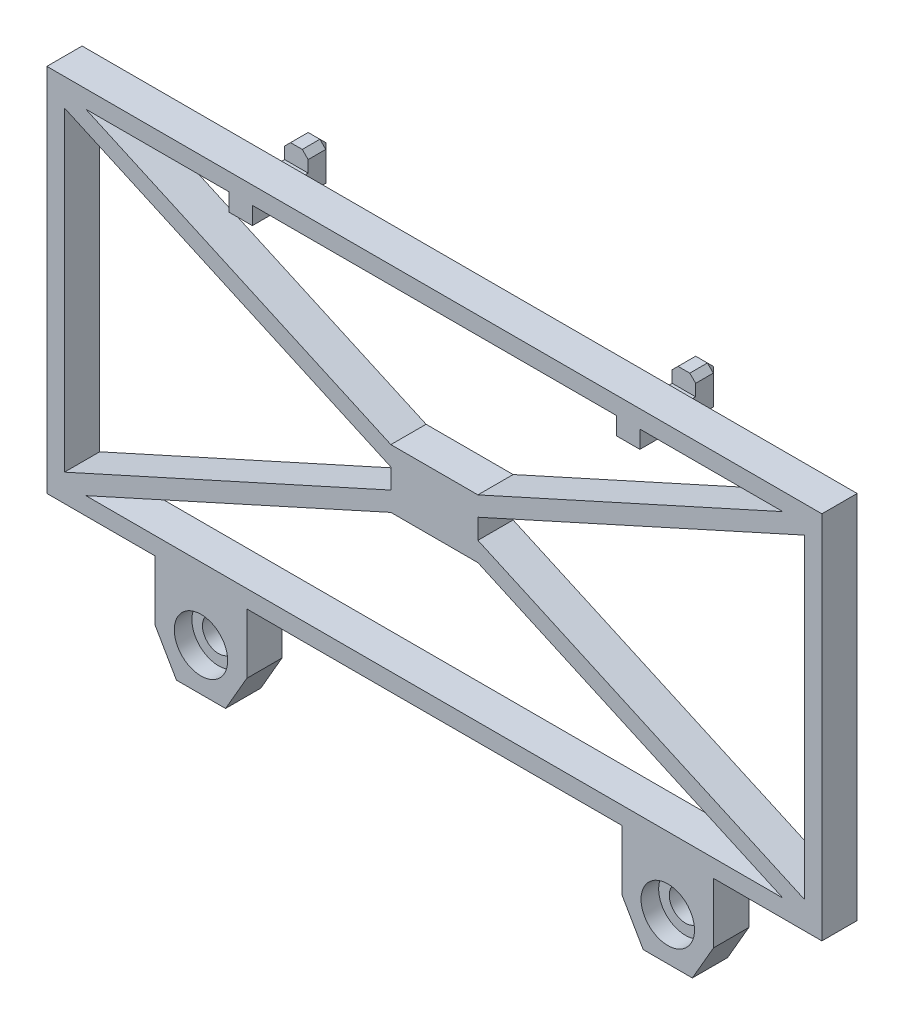
SolidWorks part; units mm, degrees
ref_plane "Front Plane" through (0, 0, 0) normal (0, 0, 1) x (1, 0, 0)
ref_plane "Top Plane" through (0, 0, 0) normal (0, 1, 0) x (1, 0, 0)
ref_plane "Right Plane" through (0, 0, 0) normal (1, 0, 0) x (0, 0, -1)
sketch "Sketch1" plane through (0, 0, 0) normal (0, 0, 1) x (1, 0, 0)
  line L0 (31.5, -14.1248) -> (31.5, -13.3017) construction
  line L5 (31.5, -13.3017) -> (3.7067, -0.7285) construction
  line L6 (3.7067, -0.7285) -> (3.7067, 0.9788) construction
  line L7 (3.7067, 0.9788) -> (31.5, 13.552) construction
  line L8 (31.5, 13.552) -> (31.5, 14.3752) construction
  line L9 (31.5, 14.3752) -> (29.6804, 14.3752) construction
  line L11 (29.6804, 14.3752) -> (3.7067, 2.6252) construction
  line L12 (3.7067, 2.6252) -> (-3.7067, 2.6252) construction
  line L13 (-3.7067, 2.6252) -> (-29.6804, 14.3752) construction
  line L14 (-29.6804, 14.3752) -> (-31.5, 14.3752) construction
  line L19 (-31.5, 14.3752) -> (-31.5, 13.552) construction
  line L20 (-31.5, 13.552) -> (-3.7067, 0.9788) construction
  line L24 (-3.7067, 0.9788) -> (-3.7067, -0.7285) construction
  line L25 (-3.7067, -0.7285) -> (-31.5, -13.3017) construction
  line L26 (-31.5, -13.3017) -> (-31.5, -14.1248) construction
  line L27 (-31.5, -14.1248) -> (-29.6804, -14.1248) construction
  line L28 (-29.6804, -14.1248) -> (-3.7067, -2.3748) construction
  line L29 (-3.7067, -2.3748) -> (3.7067, -2.3748) construction
  line L30 (3.7067, -2.3748) -> (29.6804, -14.1248) construction
  line L31 (29.6804, -14.1248) -> (31.5, -14.1248) construction
  line L32 (-33, -15.6248) -> (33, -15.6248) construction
  line L33 (33, -15.6248) -> (33, 15.8752) construction
  line L34 (33, 15.8752) -> (-33, 15.8752) construction
  line L35 (-33, 15.8752) -> (-33, -15.6248) construction
  line L36 (31.5, -14.1248) -> (31.5, -13.3017)
  line L37 (31.5, -13.3017) -> (3.7067, -0.7285)
  line L38 (3.7067, -0.7285) -> (3.7067, 0.9788)
  line L39 (3.7067, 0.9788) -> (31.5, 13.552)
  line L40 (31.5, 13.552) -> (31.5, 14.3752)
  line L41 (31.5, 14.3752) -> (29.6804, 14.3752)
  line L42 (29.6804, 14.3752) -> (3.7067, 2.6252)
  line L43 (3.7067, 2.6252) -> (-3.7067, 2.6252)
  line L44 (-3.7067, 2.6252) -> (-29.6804, 14.3752)
  line L45 (-29.6804, 14.3752) -> (-31.5, 14.3752)
  line L46 (-31.5, 14.3752) -> (-31.5, 13.552)
  line L47 (-31.5, 13.552) -> (-3.7067, 0.9788)
  line L48 (-3.7067, 0.9788) -> (-3.7067, -0.7285)
  line L49 (-3.7067, -0.7285) -> (-31.5, -13.3017)
  line L50 (-31.5, -13.3017) -> (-31.5, -14.1248)
  line L51 (-31.5, -14.1248) -> (-29.6804, -14.1248)
  line L52 (-29.6804, -14.1248) -> (-3.7067, -2.3748)
  line L53 (-3.7067, -2.3748) -> (3.7067, -2.3748)
  line L54 (3.7067, -2.3748) -> (29.6804, -14.1248)
  line L55 (29.6804, -14.1248) -> (31.5, -14.1248)
  line L56 (-33, -15.6248) -> (33, -15.6248)
  line L57 (33, -15.6248) -> (33, 15.8752)
  line L58 (33, 15.8752) -> (-33, 15.8752)
  line L59 (-33, 15.8752) -> (-33, -15.6248)
  line L60 (-31.5, 13.552) -> (-31.5, -13.3017)
  line L61 (-29.6804, -14.1248) -> (29.6804, -14.1248)
  line L62 (31.5, -13.3017) -> (31.5, 13.552)
  line L63 (-29.6804, 14.3752) -> (29.6804, 14.3752)
  point P1 (33, -15.75)
  point P2 (-33, 15.75)
  point P3 (-33, -15.75)
  point P4 (33, 15.75)
  point P6 (-32.677, -16.4269)
  point P7 (33.323, 15.0731)
  point P8 (-33.323, 15.0731)
  point P9 (32.677, -16.4269)
  point P10 (-33.323, -15.0731)
  point P11 (32.677, 16.4269)
  point P12 (-32.677, 16.4269)
  point P13 (33.323, -15.0731)
  dimension "D1" = 66
  dimension "D2" = 31.5
extrude "Boss-Extrude1" add sketch "Sketch1" along normal blind 3 contours L45 | L45 | L45 | L58 L59 L56 L57 L45 L63 L41 L40 L62 L36 L55 L61 L51 L50 L60 L46 region at (0, 0.1252, 0) region at (-32.2687, 0.1252, 0)
sketch "Sketch2" plane through (0, 0, 3) normal (0, 0, 1) x (1, 0, 0)
  line L0 (-23.7721, -15.6248) -> (-23.7721, -20.7498)
  line L1 (-23.7721, -15.6248) -> (-23.7721, -20.7498) construction
  line L2 (-23.7721, -20.7498) -> (-21.9679, -23.8748)
  line L3 (-21.9679, -23.8748) -> (-17.7821, -23.8748)
  line L4 (-17.7821, -23.8748) -> (-15.9779, -20.7498)
  line L5 (-15.9779, -20.7498) -> (-15.9779, -15.6248)
  line L6 (-15.9779, -15.6248) -> (-23.7721, -15.6248)
  line L13 (0, 15.75) -> (0, -15.75) construction
  line L14 (-21.9679, -23.8748) -> (-17.7821, -23.8748) construction
  line L22 (-33, -15.6248) -> (33, -15.6248) construction
  circle A0 centre (-19.875, -20.2498) radius 1.375
  circle A2 centre (-19.875, -20.2498) radius 2.275
  circle A4 centre (-19.875, -20.2498) radius 1.375 construction
  point P16 (-19.266, -19.2003)
  point P19 (-19.875, -23.8748)
  point P20 (-19.875, -15.6248)
  point P26 (-17.5713, -24.9932)
  point P27 (-15.2198, -15.75)
  point P28 (-24.3241, -15.75)
  point P29 (-24.6255, -19.6874)
  point P30 (0, 0)
  point P31 (-15.1595, -24.9932)
  point P32 (-19.048, -19.8539)
  point P33 (-14.1727, -15.75)
  point P37 (-23.7721, -20.7498)
  point P41 (-17.7821, -23.8748)
  point P43 (23.7721, -20.7498)
  dimension "D1" = 4.55
  dimension "D2" = 2.75
extrude "Boss-Extrude2" add sketch "Sketch2" against normal up to surface (3 mm away) contours L4 L5 L0 L2 L3 A2 | A2 A0 region at (-19.875, -15.7383, 3) region at (-22.0857, -20.2498, 3) up to face at (17.6033, 0.1252, 0)
extrude "Cut-Extrude1" cut sketch "Sketch2<4>" against normal offset from surface (1.5 mm away) 1.5 contours A2 A0 region at (-22.0857, -20.2498, 3) up to face at (17.6033, 0.1252, 0)
sketch "Sketch2<4>" plane through (0, 0, 3) normal (0, 0, 1) x (1, 0, 0) same geometry as "Sketch2"
ref_plane "Plane1" through (0, 0, 0) normal (-1, 0, 0) x (0, 0, 1)
mirror "Mirror1" about plane through (0, 0, 0) normal (-1, 0, 0) of "Boss-Extrude2", "Cut-Extrude1"
ref_plane "Plane2" through (-16.5, 0, 0) normal (-1, 0, 0) x (0, 0, 1)
sketch "Sketch3" plane through (-16.5, 0, 0) normal (-1, 0, 0) x (0, 0, 1)
  line L0 (-1.75, 14.3752) -> (3, 14.3752)
  line L1 (3, 14.3752) -> (3, 12.3752)
  line L2 (3, 12.3752) -> (-3.75, 12.3752)
  line L3 (-3.75, 12.3752) -> (-3.75, 15.8752)
  line L4 (-3.75, 15.8752) -> (-1.75, 15.8752)
  line L5 (-1.75, 15.8752) -> (-1.75, 14.3752)
  line L7 (3, 14.3752) -> (0, 14.3752) construction
  line L8 (3, -22.5248) -> (3, -17.9748) construction
  line L9 (0, 15.8752) -> (0, -15.6248) construction
  line L10 (3, 15.8752) -> (0, 15.8752) construction
  point P0 (-1.6625, 14.3752)
  dimension "D1" = 2
  dimension "D2" = 2
  dimension "D4" = 1.75
extrude "Boss-Extrude3" add sketch "Sketch3" along normal mid plane 2
chamfer "Chamfer1" distance 0.5 angle 45 9 edges at (-16.5, 12.3752, -3.75) (-17.5, 12.3752, -0.375) (-16.5, 12.3752, 3) (-15.5, 12.3752, -0.375) (-17.5, 14.1252, -3.75) (-16.5, 15.8752, -3.75) (-15.5, 14.1252, -3.75) (-17.5, 15.8752, -2.75) (-15.5, 15.8752, -2.75)
mirror "Mirror2" about plane through (0, 0, 0) normal (-1, 0, 0) of "Chamfer1", "Boss-Extrude3"
